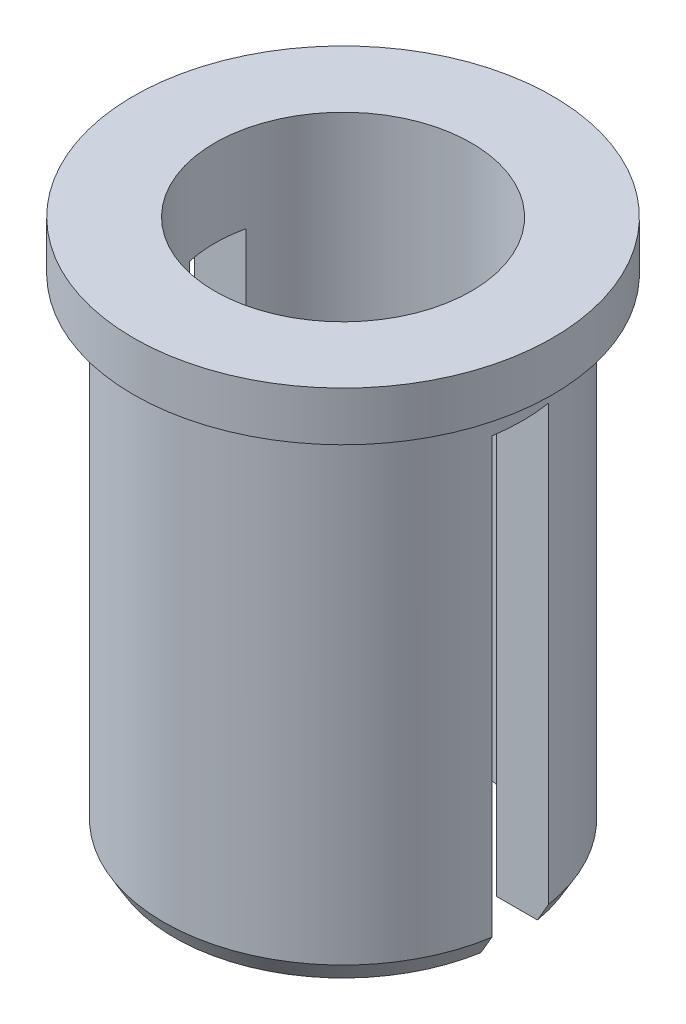
SolidWorks part; units mm, degrees
material "Brass"
ref_plane "Front Plane" through (0, 0, 0) normal (0, 0, 1) x (1, 0, 0)
ref_plane "Top Plane" through (0, 0, 0) normal (0, 1, 0) x (1, 0, 0)
ref_plane "Right Plane" through (0, 0, 0) normal (1, 0, 0) x (0, 0, -1)
ref_axis "Axis1" through (0, 0, -88.99) along (0, 0, 1)
ref_axis "Axis2" through (0, -55, 0) along (0, 1, 0)
ref_axis "Axis3" through (-88.99, 0, 0) along (1, 0, 0)
sketch "Sketch1" plane through (0, 0, 0) normal (1, 0, 0) x (0, 0, -1)
  line L0 (-4.75, -13.8) -> (-4.75, -1.4)
  line L1 (-4.75, -1.4) -> (-4.65, -1.4)
  line L2 (-4.65, -1.4) -> (-4.65, -1.3)
  line L3 (-4.65, -1.3) -> (-5.55, -1.3)
  line L4 (-5.55, -1.3) -> (-5.55, 0)
  line L5 (-5.55, 0) -> (-3.25, 0)
  line L6 (-3.25, 0) -> (-3.25, -14.3)
  line L7 (-4.4613, -14.3) -> (-3.25, -14.3)
  line L8 (0, 0) -> (0, -6.238) construction
  line L9 (-4.75, -13.8) -> (-4.4613, -14.3)
  dimension "D1" = 6.5
  dimension "D2" = 9.5
  dimension "D3" = 14.3
  dimension "D4" = 0.1
  dimension "D5" = 11.1
  dimension "D6" = 0.1
  dimension "D7" = 1.3
  dimension "D8" = 30
  dimension "D9" = 0.5
revolve "Revolve1" add sketch "Sketch1" angle 360 about L8
hole_wizard " Tapped Hole1" positions "Sketch3" profile "Sketch2" tap size "M8x1.25" standard "ANSI Metric" end condition through all
sketch "Sketch3" plane through (0, 0, 0) normal (0, 1, 0) x (1, 0, 0)
  point P0 (0, 0)
sketch "Sketch2" plane through (0, 0, 0) normal (1, 0, 0) x (0, 0, 1)
  line L0 (0, 0) -> (0, 14.3)
  line L1 (0, 14.3) -> (3.4, 14.3)
  line L2 (3.4, 14.3) -> (3.4, 0)
  line L5 (3.4, 0) -> (0, 0)
  line L11 (0, -6.35) -> (0, 107.95) construction
  dimension "Thread Major Dia." = 6.8
  dimension "Thru Tap Drill Depth" = 14.3
sketch "Sketch4" plane through (0, -14.3, 0) normal (0, -1, 0) x (1, 0, 0)
  line L0 (-4.75, 0) -> (0, 0) construction
  line L1 (-4.75, 0.75) -> (4.75, 0.75)
  line L2 (-4.75, 0.75) -> (-4.75, -0.75)
  line L3 (-4.75, -0.75) -> (4.75, -0.75)
  line L4 (4.75, 0.75) -> (4.75, -0.75)
  circle A0 centre (0, 0) radius 4.75 construction
  dimension "D1" = 1.5
extrude "Cut-Extrude1" cut sketch "Sketch4" against normal offset from surface (12 mm away) 1 up to face at (0, -1.3, 4.65)
